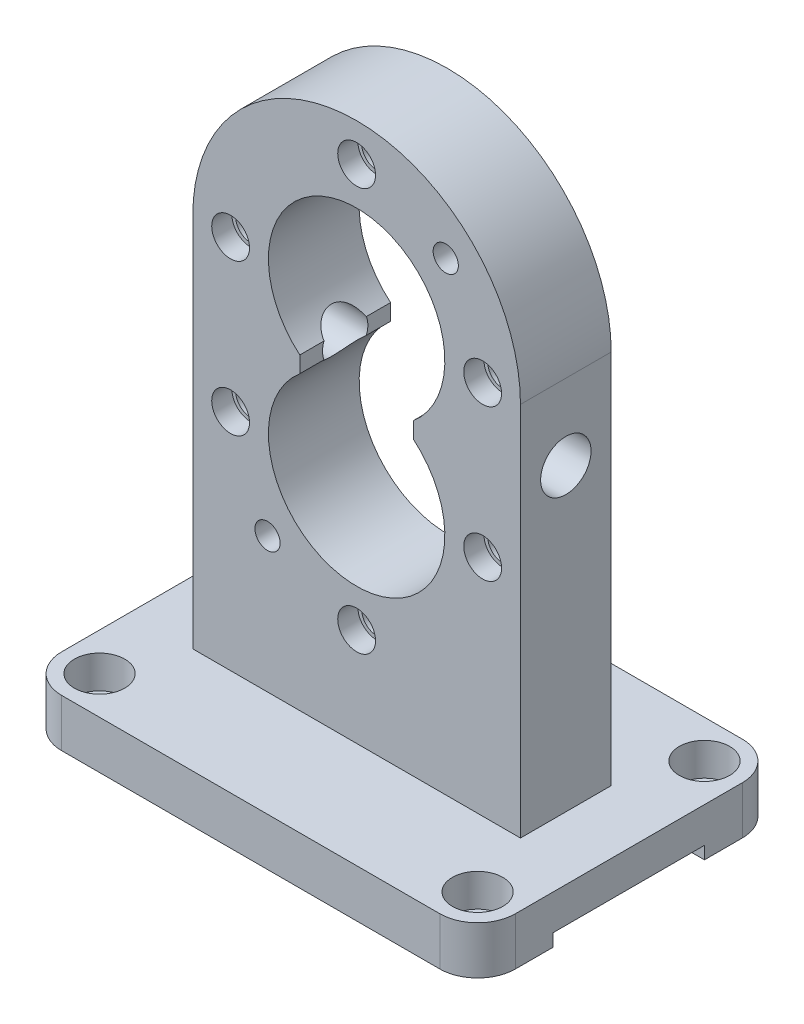
SolidWorks part; units mm, degrees
ref_plane "Front Plane" through (0, 0, 0) normal (0, 0, 1) x (1, 0, 0)
ref_plane "Top Plane" through (0, 0, 0) normal (0, 1, 0) x (1, 0, 0)
ref_plane "Right Plane" through (0, 0, 0) normal (1, 0, 0) x (0, 0, -1)
sketch "Sketch1" plane through (0, 0, 0) normal (0, 1, 0) x (1, 0, 0)
  line L1 (15, 0) -> (165, 0)
  line L2 (0, 15) -> (0, 105)
  line L3 (15, 120) -> (165, 120)
  line L4 (180, 15) -> (180, 105)
  arc A0 (165, 0) -> (180, 15) centre (165, 15) ccw
  arc A1 (180, 105) -> (165, 120) centre (165, 105) ccw
  arc A2 (15, 0) -> (0, 15) centre (15, 15) cw
  arc A3 (0, 105) -> (15, 120) centre (15, 105) cw
  circle A4 centre (15, 105) radius 10
  circle A5 centre (165, 105) radius 10
  circle A6 centre (165, 15) radius 10
  circle A7 centre (15, 15) radius 10
  circle A8 centre (15, 15) radius 7.5
  circle A9 centre (15, 105) radius 7.5
  circle A10 centre (165, 105) radius 7.5
  circle A11 centre (165, 15) radius 7.5
  point P7 (180, 0)
  point P10 (180, 120)
  point P13 (0, 0)
  point P16 (0, 120)
  dimension "D3" = 15
  dimension "D4" = 20
  dimension "D5" = 20
  dimension "D6" = 20
  dimension "D7" = 20
  dimension "D8" = 15
  dimension "D9" = 15
  dimension "D10" = 15
  dimension "D11" = 15
  dimension "D1" = 180
  dimension "D2" = 120
extrude "Boss-Extrude1" add sketch "Sketch1" along normal blind 19 contours A3 L2 A2 L1 A0 L4 A1 L3 A7 A6 A5 A4 | A5 A10 | A4 A9 | A8 | A6 A11 | A7 region at (90, 0, -60) region at (5.2828, 0, -105) region at (155.2828, 0, -105) region at (155.2828, 0, -15) region at (15, 0, -15)
extrude "Cut-Extrude1" cut sketch "Sketch1<3>" along normal blind 13 contours A5 A10 | A6 A11 | A4 A9 | A7 A8 region at (5.2828, 0, -105) region at (155.2828, 0, -105) region at (155.2828, 0, -15) region at (5.2828, 0, -15)
sketch "Sketch1<3>" plane through (0, 0, 0) normal (0, 1, 0) x (1, 0, 0) same geometry as "Sketch1"
ref_plane "Plane1" through (0, 0, -60) normal (0, 0, 1) x (1, 0, 0)
sketch "Sketch2" plane through (0, 0, -60) normal (0, 0, 1) x (1, 0, 0)
  line L0 (90, 0) -> (90, 246.4784) construction
  line L1 (25, 0) -> (155, 0)
  line L2 (25, 0) -> (25, 168)
  line L4 (155, 0) -> (155, 168)
  line L5 (0, 0) -> (180, 0) construction
  line L6 (67.4603, 141.2238) -> (67.4603, 134.7762)
  line L7 (112.5397, 141.2238) -> (112.5397, 134.7762)
  line L8 (155, 168) -> (25, 168) construction
  line L9 (155, 108) -> (25, 108) construction
  line L10 (90, 168) -> (151.8605, 229.8605) construction
  line L11 (90, 108) -> (38.785, 56.785) construction
  arc A0 (155, 168) -> (25, 168) centre (90, 168) ccw
  arc A1 (112.5397, 141.2238) -> (67.4603, 141.2238) centre (90, 168) ccw
  arc A2 (67.4603, 134.7762) -> (112.5397, 134.7762) centre (90, 108) ccw
  circle A3 centre (90, 168) radius 50 construction
  circle A4 centre (90, 108) radius 50 construction
  circle A5 centre (90, 218) radius 6
  circle A6 centre (140, 168) radius 6
  circle A7 centre (90, 58) radius 6
  circle A8 centre (40, 168) radius 6
  circle A9 centre (40, 108) radius 6
  circle A10 centre (140, 108) radius 6
  circle A11 centre (54.6447, 72.6447) radius 5
  circle A12 centre (125.3553, 203.3553) radius 5
  point P8 (90, 0)
  point P9 (90, 0)
  dimension "D1" = 130
  dimension "D5" = 70
  dimension "D6" = 70
  dimension "D7" = 100
  dimension "D8" = 100
  dimension "D10" = 12
  dimension "D11" = 12
  dimension "D12" = 12
  dimension "D13" = 12
  dimension "D14" = 12
  dimension "D15" = 12
  dimension "D18" = 10
  dimension "D19" = 10
  dimension "D2" = 168
  dimension "D3" = 130
  dimension "D4" = 60
  dimension "D9" = 6.4477
  dimension "D16" = 45
  dimension "D17" = 45
extrude "Boss-Extrude3" add sketch "Sketch2" along normal mid plane 36
sketch "Sketch3" plane through (180, 0, 0) normal (1, 0, 0) x (0, 0, -1)
  line L0 (0, 0) -> (120, 0)
  line L5 (0, 0) -> (120, 0) construction
  line L8 (30, -5) -> (90, -5)
  line L9 (30, -5) -> (30, 5)
  line L10 (30, 5) -> (90, 5)
  line L11 (90, -5) -> (90, 5)
  line L12 (30, -5) -> (90, 5) construction
  line L13 (30, 5) -> (90, -5) construction
  point P0 (60, 0)
  dimension "D1" = 5
  dimension "D2" = 60
sketch "Sketch11" plane through (0, 0, 0) normal (0, -1, 0) x (1, 0, 0)
  circle A0 centre (15, -15) radius 7.5
  circle A1 centre (15, -15) radius 10
  circle A2 centre (165, -15) radius 7.5
  circle A3 centre (165, -15) radius 10
  circle A4 centre (165, -105) radius 10
  circle A5 centre (165, -105) radius 7.5
  circle A6 centre (15, -105) radius 7.5
  circle A7 centre (15, -105) radius 10
  dimension "D1" = 20
  dimension "D2" = 15
  dimension "D3" = 20
  dimension "D4" = 15
  dimension "D5" = 15
  dimension "D6" = 20
  dimension "D7" = 20
  dimension "D8" = 15
extrude "Boss-Extrude4" add sketch "Sketch11" against normal blind 13
sketch "Sketch12" plane through (0, 19, 0) normal (0, 1, 0) x (1, 0, 0)
  circle A0 centre (15, 105) radius 10
  circle A1 centre (165, 105) radius 10
  circle A2 centre (165, 15) radius 10
  circle A3 centre (15, 15) radius 10
  dimension "D1" = 20
  dimension "D2" = 20
  dimension "D3" = 20
  dimension "D4" = 20
extrude "Cut-Extrude7" cut sketch "Sketch12" against normal blind 13
extrude "Cut-Extrude2" cut sketch "Sketch3" against normal blind 180 contours L0 L11 L10 L9 region at (180, 2.5, -60)
sketch "Sketch4" plane through (0, 0, -78) normal (0, 0, -1) x (-1, 0, 0)
  circle A0 centre (-90, 218) radius 7.5
  circle A1 centre (-40, 168) radius 7.5
  circle A2 centre (-40, 108) radius 7.5
  circle A3 centre (-90, 58) radius 7.5
  circle A4 centre (-140, 108) radius 7.5
  circle A5 centre (-140, 168) radius 7.5
  dimension "D1" = 15
  dimension "D2" = 15
  dimension "D3" = 15
  dimension "D4" = 15
  dimension "D5" = 15
  dimension "D6" = 15
extrude "Cut-Extrude3" cut sketch "Sketch4" against normal blind 8
mirror "Mirror1" about plane through (0, 0, -60) normal (0, 0, 1) of "Cut-Extrude3"
sketch "Sketch5" plane through (25, 0, 0) normal (-1, 0, 0) x (0, 0, 1)
  line L1 (-60, 168) -> (-60, -3.7766) construction
  line L2 (-42, 168) -> (-78, 168) construction
  line L3 (-60, -10.45) -> (-60, 10.45) construction
  line L4 (-90, 0) -> (-105, 0) construction
  circle A0 centre (-60, 138) radius 9
  dimension "D2" = 18
  dimension "D1" = 138
extrude "Cut-Extrude4" cut sketch "Sketch5" against normal blind 130 contours A0
sketch "Sketch6" plane through (25, 0, 0) normal (-1, 0, 0) x (0, 0, 1)
  circle A0 centre (-60, 138) radius 11
  dimension "D1" = 22
extrude "Cut-Extrude5" cut sketch "Sketch6" against normal blind 15
sketch "Sketch7" plane through (155, 0, 0) normal (1, 0, 0) x (0, 0, -1)
  circle A0 centre (60, 138) radius 10
  dimension "D1" = 20
extrude "Cut-Extrude6" cut sketch "Sketch7" against normal blind 15
